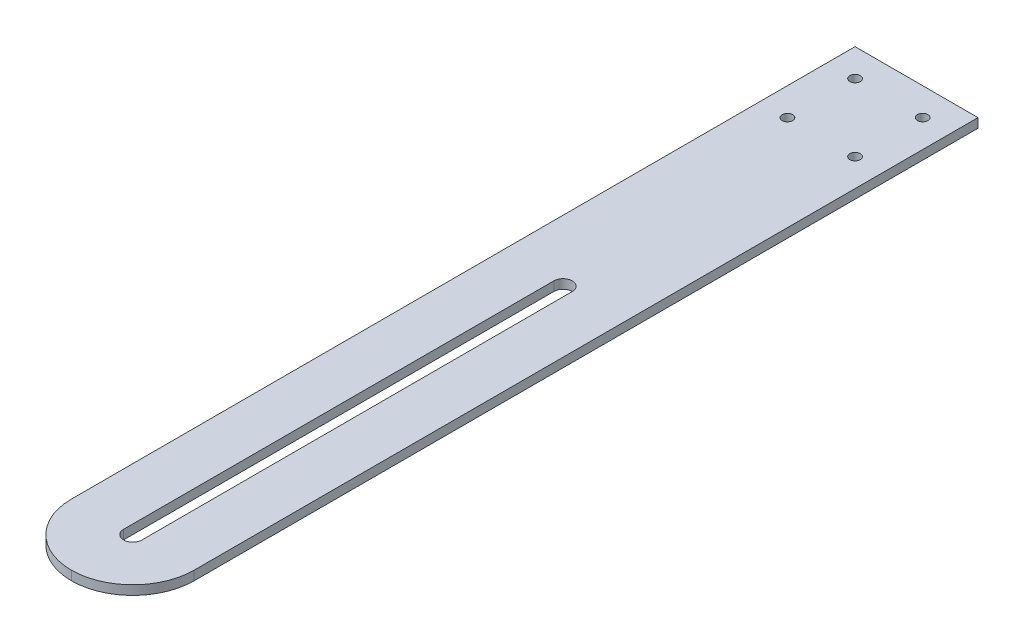
SolidWorks part; units mm, degrees
ref_plane "Front Plane" through (0, 0, 0) normal (0, 0, 1) x (1, 0, 0)
ref_plane "Top Plane" through (0, 0, 0) normal (0, 1, 0) x (1, 0, 0)
ref_plane "Right Plane" through (0, 0, 0) normal (1, 0, 0) x (0, 0, -1)
sketch "Sketch1" plane through (0, 0, 0) normal (0, 1, 0) x (1, 0, 0)
  line L1 (20, 137.5) -> (-20, 137.5)
  line L2 (20, 137.5) -> (20, -137.5)
  line L3 (20, -137.5) -> (-20, -137.5)
  line L4 (-20, 137.5) -> (-20, -137.5)
  line L5 (20, 137.5) -> (-20, -137.5) construction
  line L6 (20, -137.5) -> (-20, 137.5) construction
  point P0 (0, 0)
  dimension "D1" = 275
  dimension "D2" = 40
extrude "Boss-Extrude1" add sketch "Sketch1" along normal blind 3
sketch "Sketch2" plane through (0, 3, 0) normal (0, 1, 0) x (1, 0, 0)
  line L0 (-20, 97.5) -> (20, 97.5) construction
  line L1 (-20, 137.5) -> (-20, -137.5) construction
  line L2 (20, -137.5) -> (20, 137.5) construction
  line L3 (20, 137.5) -> (-20, 137.5) construction
  circle A0 centre (-11, 128.5) radius 1.7
  circle A1 centre (-11, 106.5) radius 1.7
  circle A2 centre (11, 128.5) radius 1.7
  circle A3 centre (11, 106.5) radius 1.7
  dimension "D1" = 3.4
  dimension "D2" = 3.4
  dimension "D3" = 3.4
  dimension "D4" = 3.4
  dimension "D6" = 9
  dimension "D7" = 9
  dimension "D8" = 9
  dimension "D9" = 9
  dimension "D5" = 40
extrude "Cut-Extrude1" cut sketch "Sketch2" against normal through all
fillet "Fillet1" radius 20 2 edges at (-20, 1.5, 137.5) (20, 1.5, 137.5)
sketch "Sketch3" plane through (0, 3, 0) normal (0, 1, 0) x (1, 0, 0)
  line L2 (-3, 22.5) -> (-3, -117.5)
  line L3 (3, 22.5) -> (3, -117.5)
  arc A3 (-3, 22.5) -> (3, 22.5) centre (0, 22.5) cw
  arc A4 (-3, -117.5) -> (3, -117.5) centre (0, -117.5) ccw
  point P1 (0, 25.5)
  dimension "D4" = 20
  dimension "D1" = 140
  dimension "D3" = 6
extrude "Cut-Extrude2" cut sketch "Sketch3" against normal through all
